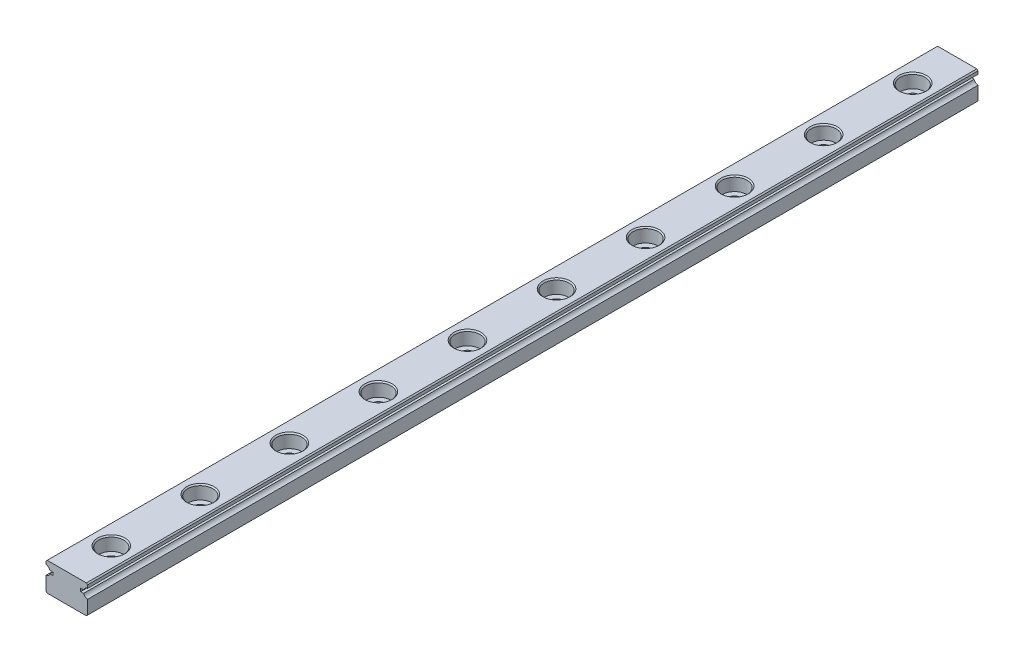
SolidWorks part; units mm, degrees
ref_plane "Спереди" through (0, 0, 0) normal (0, 0, 1) x (1, 0, 0)
ref_plane "Сверху" through (0, 0, 0) normal (0, 1, 0) x (1, 0, 0)
ref_plane "Справа" through (0, 0, 0) normal (1, 0, 0) x (0, 0, -1)
sketch "Sketch1" plane through (0, 0, 0) normal (0, 0, 1) x (1, 0, 0)
  line L0 (0, 0) -> (0, 4.3706) construction
  line L1 (-3.3, -2.4) -> (3.3, -2.4)
  line L2 (-3.5, -2.2) -> (-3.5, 0.1063)
  line L3 (-3.3, 2.4) -> (3.3, 2.4)
  line L4 (3.5, -2.2) -> (3.5, 0.1063)
  line L5 (-3.5, -2.4) -> (3.5, 2.4) construction
  line L6 (-3.5, 2.4) -> (3.5, -2.4) construction
  line L7 (-3.5, 1.6937) -> (-3.5, 2.2)
  line L8 (3.5, 1.6937) -> (3.5, 2.2)
  line L9 (-3.5, -2.2) -> (-3.3, -2.4)
  line L10 (3.3, -2.4) -> (3.5, -2.2)
  line L11 (3.3, 2.4) -> (3.5, 2.2)
  line L12 (-3.5, 2.2) -> (-3.3, 2.4)
  line L13 (2.8401, 0.65) -> (2.3401, 0.65)
  line L14 (-2.8401, 0.65) -> (-2.3401, 0.65)
  line L15 (2.3401, 0.65) -> (2.3401, 1.15)
  line L16 (-2.8401, 1.15) -> (-2.3401, 1.15)
  line L17 (-2.3401, 0.65) -> (-2.3401, 1.15)
  line L18 (2.8401, 1.15) -> (2.3401, 1.15)
  arc A0 (-3.5, 1.6937) -> (-2.8401, 1.15) centre (-3.6, 0.9) cw
  arc A1 (3.5, 1.6937) -> (2.8401, 1.15) centre (3.6, 0.9) ccw
  arc A2 (-2.8401, 0.65) -> (-3.5, 0.1063) centre (-3.6, 0.9) cw
  arc A3 (2.8401, 0.65) -> (3.5, 0.1063) centre (3.6, 0.9) ccw
  point P0 (0, 0)
  dimension "D4" = 0.8
  dimension "D5" = 0.1
  dimension "D1" = 7
  dimension "D2" = 4.8
  dimension "D3" = 1.5
  dimension "D6" = 0.5
  dimension "D7" = 0.5
extrude "Extrude1" add sketch "Sketch1" along normal blind 150
sketch "Sketch2" plane through (0, 2.4, 0) normal (0, 1, 0) x (1, 0, 0)
  line L0 (0, 0) -> (0, -7.5) construction
  circle A0 centre (0, -7.5) radius 1.2
  circle A1 centre (0, -7.5) radius 2.1
  dimension "D1" = 2.4
  dimension "D2" = 4.2
  dimension "D3" = 7.5
extrude "Extrude2" cut sketch "Sketch2" against normal up to next contours A0 region at (0, 2.4, 7.5)
extrude "Extrude4" cut sketch "Sketch" against normal blind 2.3
sketch "Sketch" plane through (0, 2.4, 0) normal (0, 1, 0) x (1, 0, 0) same geometry as "Sketch2"
chamfer "Chamfer1" distance 0.2 angle 45 2 edges at (0, -2.4, 8.7) (0, 2.4, 9.6)
pattern_linear "LPattern1" count 10 spacing 15 along (0, 0, 1) of "Extrude4", "Chamfer1", "Extrude2"
